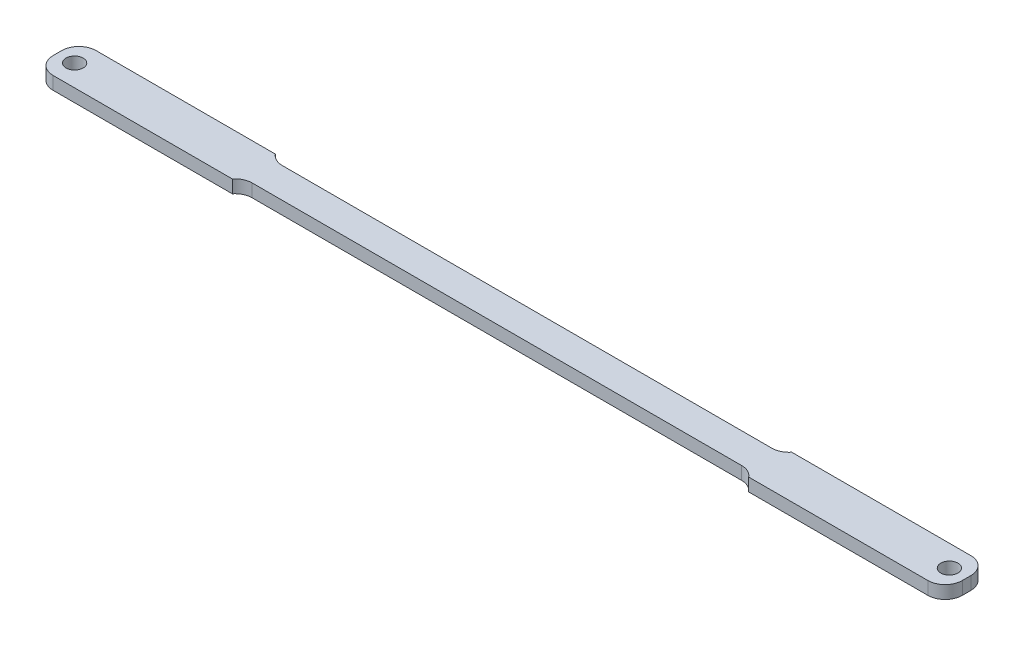
SolidWorks part; units mm, degrees
ref_plane "Front Plane" through (0, 0, 0) normal (0, 0, 1) x (1, 0, 0)
ref_plane "Top Plane" through (0, 0, 0) normal (0, 1, 0) x (1, 0, 0)
ref_plane "Right Plane" through (0, 0, 0) normal (1, 0, 0) x (0, 0, -1)
sketch "Sketch2" plane through (0, 0, 0) normal (0, 1, 0) x (1, 0, 0)
  line L1 (-50.82, 2.5) -> (50.82, 2.5)
  line L2 (-52.82, 0.5) -> (-52.82, -0.5)
  line L3 (-50.82, -2.5) -> (50.82, -2.5)
  line L4 (52.82, 0.5) -> (52.82, -0.5)
  line L5 (-52.82, 2.5) -> (52.82, -2.5) construction
  line L6 (-52.82, -2.5) -> (52.82, 2.5) construction
  circle A0 centre (-50.82, 0) radius 1
  circle A1 centre (50.82, 0) radius 1
  arc A2 (50.82, -2.5) -> (52.82, -0.5) centre (50.82, -0.5) ccw
  arc A3 (50.82, 2.5) -> (52.82, 0.5) centre (50.82, 0.5) cw
  arc A4 (-52.82, -0.5) -> (-50.82, -2.5) centre (-50.82, -0.5) ccw
  arc A5 (-50.82, 2.5) -> (-52.82, 0.5) centre (-50.82, 0.5) ccw
  point P0 (0, 0)
  dimension "D3" = 2
  dimension "D5" = 2
  dimension "D7" = 2
  dimension "D1" = 105.64
  dimension "D2" = 5
  dimension "D4" = 2
  dimension "D6" = 2
extrude "Boss-Extrude1" add sketch "Sketch2" along normal blind 1.5
sketch "Sketch3" plane through (0, 1.5, 0) normal (0, 1, 0) x (1, 0, 0)
  line L0 (50.82, 2.5) -> (-50.82, 2.5) construction
  line L1 (-30, 3.25) -> (30, 3.25)
  line L2 (-30, 3.25) -> (-30, 1.75)
  line L3 (-30, 1.75) -> (30, 1.75)
  line L4 (30, 3.25) -> (30, 1.75)
  line L5 (-30, 3.25) -> (30, 1.75) construction
  line L6 (-30, 1.75) -> (30, 3.25) construction
  line L7 (-50.82, -2.5) -> (50.82, -2.5) construction
  line L8 (-30, -1.75) -> (30, -1.75)
  line L9 (-30, -1.75) -> (-30, -3.25)
  line L10 (-30, -3.25) -> (30, -3.25)
  line L11 (30, -1.75) -> (30, -3.25)
  line L12 (-30, -1.75) -> (30, -3.25) construction
  line L13 (-30, -3.25) -> (30, -1.75) construction
  point P0 (0, 2.5)
  point P7 (0, -2.5)
  dimension "D1" = 1.5
  dimension "D2" = 1.5
  dimension "D3" = 60
  dimension "D4" = 60
extrude "Cut-Extrude1" cut sketch "Sketch3" against normal through all
fillet "Fillet1" radius 2 4 edges at (30, 0.75, -1.75) (30, 0.75, 1.75) (-30, 0.75, 1.75) (-30, 0.75, -1.75)
